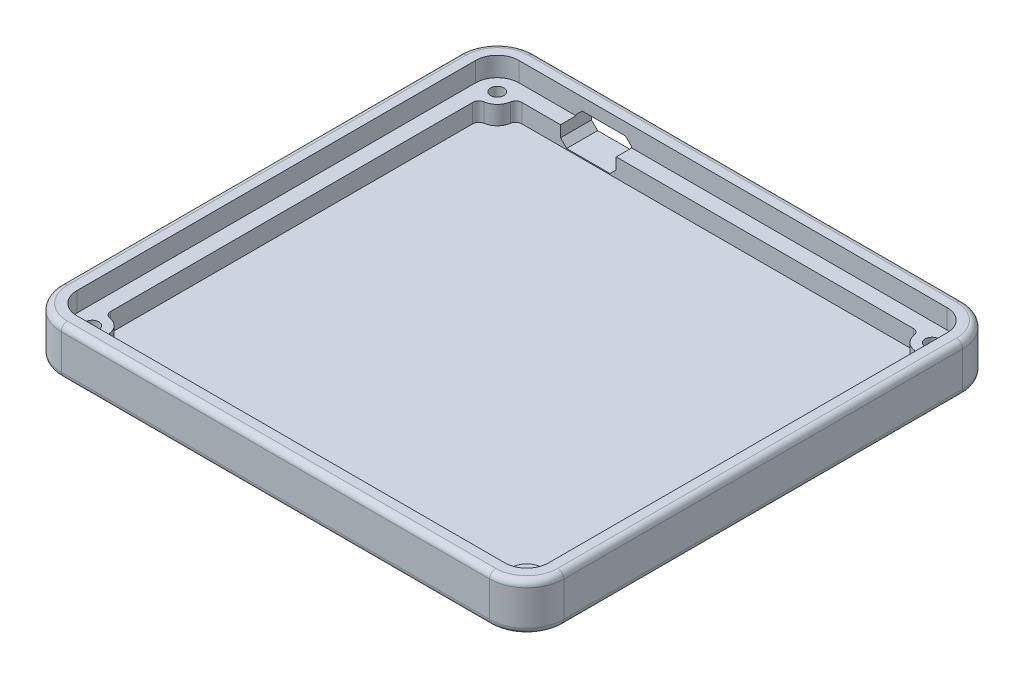
SolidWorks part; units mm, degrees
material "ABS"
ref_plane "Front Plane" through (0, 0, 0) normal (0, 0, 1) x (1, 0, 0)
ref_plane "Top Plane" through (0, 0, 0) normal (0, 1, 0) x (1, 0, 0)
ref_plane "Right Plane" through (0, 0, 0) normal (1, 0, 0) x (0, 0, -1)
sketch "Sketch2" plane through (0, 0, 0) normal (0, 1, 0) x (1, 0, 0)
  line L1 (-69.195, 71.435) -> (69.195, 71.435)
  line L2 (-76.195, 64.435) -> (-76.195, -64.435)
  line L3 (-69.195, -71.435) -> (69.195, -71.435)
  line L4 (76.195, 64.435) -> (76.195, -64.435)
  line L5 (-76.195, 71.435) -> (76.195, -71.435) construction
  line L6 (-76.195, -71.435) -> (76.195, 71.435) construction
  arc A0 (-76.195, -64.435) -> (-69.195, -71.435) centre (-69.195, -64.435) ccw
  arc A1 (-69.195, 71.435) -> (-76.195, 64.435) centre (-69.195, 64.435) ccw
  arc A2 (69.195, 71.435) -> (76.195, 64.435) centre (69.195, 64.435) cw
  arc A3 (69.195, -71.435) -> (76.195, -64.435) centre (69.195, -64.435) ccw
  point P0 (0, 0)
  dimension "D3" = 7
  dimension "D1" = 152.39
  dimension "D2" = 142.87
extrude "Boss-Extrude2" add sketch "Sketch2" along normal blind 3
sketch "Sketch3" plane through (0, 3, 0) normal (0, 1, 0) x (1, 0, 0)
  line L0 (-69.195, -71.435) -> (69.195, -71.435) construction
  line L1 (76.195, -64.435) -> (76.195, 64.435) construction
  line L2 (69.195, 71.435) -> (-69.195, 71.435) construction
  line L3 (-76.195, 64.435) -> (-76.195, -64.435) construction
  line L4 (-69.195, -71.435) -> (69.195, -71.435)
  line L5 (76.195, -64.435) -> (76.195, 64.435)
  line L6 (69.195, 71.435) -> (-69.195, 71.435)
  line L7 (-76.195, 64.435) -> (-76.195, -64.435)
  line L8 (0, -80.5945) -> (0, 82.9206) construction
  line L9 (9.041, 0) -> (-113.0904, 0) construction
  line L10 (-81.195, 64.435) -> (-81.195, -64.435)
  line L11 (-69.195, -76.435) -> (69.195, -76.435)
  line L12 (81.195, -64.435) -> (81.195, 64.435)
  line L13 (69.195, 76.435) -> (-69.195, 76.435)
  line L14 (-71.195, 60.44) -> (-71.195, -60.44)
  line L15 (-65.2, -66.435) -> (65.2, -66.435)
  line L16 (71.195, -60.44) -> (71.195, 60.44)
  line L17 (65.2, 66.435) -> (-65.2, 66.435)
  line L18 (-71.195, 60.44) -> (-70.195, 60.44)
  line L19 (-65.2, 66.435) -> (-65.2, 65.435)
  line L20 (-71.195, 64.435) -> (-71.195, -64.435) construction
  line L21 (69.195, 66.435) -> (-69.195, 66.435) construction
  line L22 (65.2, 66.435) -> (65.2, 65.435)
  line L23 (71.195, 60.44) -> (70.195, 60.44)
  line L24 (65.2, -66.435) -> (65.2, -65.435)
  line L25 (71.195, -60.44) -> (70.195, -60.44)
  line L26 (-65.2, -66.435) -> (-65.2, -65.435)
  line L27 (-71.195, -60.44) -> (-70.195, -60.44)
  line L28 (-69.195, -66.435) -> (69.195, -66.435) construction
  line L29 (71.195, -64.435) -> (71.195, 64.435) construction
  arc A0 (-76.195, -64.435) -> (-69.195, -71.435) centre (-69.195, -64.435) ccw construction
  arc A1 (69.195, -71.435) -> (76.195, -64.435) centre (69.195, -64.435) ccw construction
  arc A2 (76.195, 64.435) -> (69.195, 71.435) centre (69.195, 64.435) ccw construction
  arc A3 (-69.195, 71.435) -> (-76.195, 64.435) centre (-69.195, 64.435) ccw construction
  arc A4 (-76.195, -64.435) -> (-69.195, -71.435) centre (-69.195, -64.435) ccw
  arc A5 (69.195, -71.435) -> (76.195, -64.435) centre (69.195, -64.435) ccw
  arc A6 (76.195, 64.435) -> (69.195, 71.435) centre (69.195, 64.435) ccw
  arc A7 (-69.195, 71.435) -> (-76.195, 64.435) centre (-69.195, 64.435) ccw
  circle A9 centre (-70.2, -65.44) radius 2.15
  circle A10 centre (70.2, -65.44) radius 2.15
  circle A11 centre (70.2, 65.44) radius 2.15
  circle A12 centre (-70.2, 65.44) radius 2.15
  arc A13 (-81.195, -64.435) -> (-69.195, -76.435) centre (-69.195, -64.435) ccw
  arc A14 (69.195, -76.435) -> (81.195, -64.435) centre (69.195, -64.435) ccw
  arc A15 (81.195, 64.435) -> (69.195, 76.435) centre (69.195, 64.435) ccw
  arc A16 (-69.195, 76.435) -> (-81.195, 64.435) centre (-69.195, 64.435) ccw
  arc A21 (-70.195, 60.44) -> (-65.2, 65.435) centre (-70.195, 65.435) ccw
  arc A22 (70.195, 60.44) -> (65.2, 65.435) centre (70.195, 65.435) cw
  arc A23 (-69.195, 66.435) -> (-71.195, 64.435) centre (-69.195, 64.435) ccw construction
  arc A24 (70.195, -60.44) -> (65.2, -65.435) centre (70.195, -65.435) ccw
  arc A25 (-70.195, -60.44) -> (-65.2, -65.435) centre (-70.195, -65.435) cw
  arc A26 (-71.195, -64.435) -> (-69.195, -66.435) centre (-69.195, -64.435) ccw construction
  arc A27 (69.195, -66.435) -> (71.195, -64.435) centre (69.195, -64.435) ccw construction
  arc A28 (71.195, 64.435) -> (69.195, 66.435) centre (69.195, 64.435) ccw construction
  arc M10 (-76.195, -64.435) -> (-69.195, -71.435) centre (-69.195, -64.435) ccw
  line M11 (-69.195, -71.435) -> (69.195, -71.435)
  arc M12 (69.195, -71.435) -> (76.195, -64.435) centre (69.195, -64.435) ccw
  line M13 (76.195, -64.435) -> (76.195, 64.435)
  arc M14 (76.195, 64.435) -> (69.195, 71.435) centre (69.195, 64.435) ccw
  line M15 (69.195, 71.435) -> (-69.195, 71.435)
  arc M16 (-69.195, 71.435) -> (-76.195, 64.435) centre (-69.195, 64.435) ccw
  line M17 (-76.195, 64.435) -> (-76.195, -64.435)
  dimension "D1" = 65.44
  dimension "D2" = 4.3
  dimension "D3" = 70.2
  dimension "D4" = 5
  dimension "D6" = 1
  dimension "D7" = 5
  dimension "D8" = 1
  dimension "D9" = 5
  dimension "D5" = 5
extrude "Boss-Extrude3" add sketch "Sketch3" along normal blind 6 and the other way blind 3 contours L13 A16 L10 A13 L11 A14 L12 A15 M10 M17 M16 M15 M14 M13 M12 M11 | L17 L16 L15 L14 M17 M10 M11 M12 M13 M14 M15 M16 region at (-72.6677, 3, 67.9077) region at (-76.1033, 3, -71.3433)
sketch "Sketch8" plane through (0, 9, 0) normal (0, 1, 0) x (1, 0, 0)
  line L0 (-69.195, -76.435) -> (69.195, -76.435) construction
  line L1 (81.195, -64.435) -> (81.195, 64.435) construction
  line L2 (69.195, 76.435) -> (-69.195, 76.435) construction
  line L3 (-81.195, 64.435) -> (-81.195, -64.435) construction
  line L4 (76.195, -64.435) -> (76.195, 64.435)
  line L5 (69.195, 71.435) -> (-69.195, 71.435)
  line L6 (-76.195, 64.435) -> (-76.195, -64.435)
  line L7 (-69.195, -71.435) -> (69.195, -71.435)
  line L8 (76.195, -64.435) -> (76.195, 64.435)
  line L9 (69.195, 71.435) -> (-69.195, 71.435)
  line L10 (-76.195, 64.435) -> (-76.195, -64.435)
  line L11 (-69.195, -71.435) -> (69.195, -71.435)
  line L12 (-69.195, -76.435) -> (69.195, -76.435)
  line L13 (81.195, -64.435) -> (81.195, 64.435)
  line L14 (69.195, 76.435) -> (-69.195, 76.435)
  line L15 (-81.195, 64.435) -> (-81.195, -64.435)
  line L16 (-76.195, 64.435) -> (-76.195, -64.435)
  line L17 (-69.195, -71.435) -> (69.195, -71.435)
  line L18 (76.195, -64.435) -> (76.195, 64.435)
  line L19 (69.195, 71.435) -> (-69.195, 71.435)
  arc A0 (-81.195, -64.435) -> (-69.195, -76.435) centre (-69.195, -64.435) ccw construction
  arc A1 (69.195, -76.435) -> (81.195, -64.435) centre (69.195, -64.435) ccw construction
  arc A2 (81.195, 64.435) -> (69.195, 76.435) centre (69.195, 64.435) ccw construction
  arc A3 (-69.195, 76.435) -> (-81.195, 64.435) centre (-69.195, 64.435) ccw construction
  arc A4 (76.195, 64.435) -> (69.195, 71.435) centre (69.195, 64.435) ccw
  arc A5 (-69.195, 71.435) -> (-76.195, 64.435) centre (-69.195, 64.435) ccw
  arc A6 (-76.195, -64.435) -> (-69.195, -71.435) centre (-69.195, -64.435) ccw
  arc A7 (69.195, -71.435) -> (76.195, -64.435) centre (69.195, -64.435) ccw
  arc A8 (76.195, 64.435) -> (69.195, 71.435) centre (69.195, 64.435) ccw
  arc A9 (-69.195, 71.435) -> (-76.195, 64.435) centre (-69.195, 64.435) ccw
  arc A10 (-76.195, -64.435) -> (-69.195, -71.435) centre (-69.195, -64.435) ccw
  arc A11 (69.195, -71.435) -> (76.195, -64.435) centre (69.195, -64.435) ccw
  arc A12 (-81.195, -64.435) -> (-69.195, -76.435) centre (-69.195, -64.435) ccw
  arc A13 (69.195, -76.435) -> (81.195, -64.435) centre (69.195, -64.435) ccw
  arc A14 (81.195, 64.435) -> (69.195, 76.435) centre (69.195, 64.435) ccw
  arc A15 (-69.195, 76.435) -> (-81.195, 64.435) centre (-69.195, 64.435) ccw
  arc A16 (-76.195, -64.435) -> (-69.195, -71.435) centre (-69.195, -64.435) ccw
  arc A17 (69.195, -71.435) -> (76.195, -64.435) centre (69.195, -64.435) ccw
  arc A18 (76.195, 64.435) -> (69.195, 71.435) centre (69.195, 64.435) ccw
  arc A19 (-69.195, 71.435) -> (-76.195, 64.435) centre (-69.195, 64.435) ccw
  line M17 (69.195, 76.435) -> (-69.195, 76.435)
  arc M18 (-69.195, 76.435) -> (-81.195, 64.435) centre (-69.195, 64.435) ccw
  line M19 (-81.195, 64.435) -> (-81.195, -64.435)
  arc M20 (-81.195, -64.435) -> (-69.195, -76.435) centre (-69.195, -64.435) ccw
  line M21 (-69.195, -76.435) -> (69.195, -76.435)
  arc M22 (69.195, -76.435) -> (81.195, -64.435) centre (69.195, -64.435) ccw
  line M23 (81.195, -64.435) -> (81.195, 64.435)
  arc M24 (81.195, 64.435) -> (69.195, 76.435) centre (69.195, 64.435) ccw
  dimension "D1" = 0
  dimension "D2" = 5
extrude "Boss-Extrude4" add sketch "Sketch8" along normal blind 6.28 contours A11 L11 A10 L10 A9 L9 A8 L8 M24 M17 M18 M19 M20 M21 M22 M23 region at (-76.1033, 9, 71.3433)
sketch "Sketch9" plane through (0, 0, -76.435) normal (0, 0, -1) x (-1, 0, 0)
  line L0 (81.195, 0) -> (81.195, 15.28) construction
  line L7 (48.765, 11.345) -> (34.765, 11.345)
  line L8 (34.765, 11.345) -> (32.765, 9.345)
  line L14 (50.765, 9.345) -> (48.765, 11.345)
  line L15 (54.9775, 7.345) -> (29.0731, 7.345) construction
  line L16 (32.765, 9.345) -> (32.765, 5.345)
  line L17 (50.765, 9.345) -> (50.765, 5.345)
  line L18 (41.765, 11.345) -> (41.765, 5.8424) construction
  line L19 (-69.195, 0) -> (69.195, 0) construction
  line L20 (50.765, 5.345) -> (48.765, 3.345)
  line L21 (48.765, 3.345) -> (34.765, 3.345)
  line L22 (34.765, 3.345) -> (32.765, 5.345)
  point P7 (50.765, 7.345)
  point P20 (32.765, 7.345)
  dimension "D2" = 7.345
  dimension "D1" = 39.43
  dimension "D5" = 4
  dimension "D6" = 2
  dimension "D7" = 18
  dimension "D8" = 14
extrude "Cut-Extrude1" cut sketch "Sketch9" against normal blind 10
fillet "Fillet1" radius 2 8 edges at (-65.2, 6, -66.435) (-71.195, 6, -60.44) (-71.195, 6, 60.44) (-65.2, 6, 66.435) (71.195, 6, 60.44) (65.2, 6, 66.435) (65.2, 6, -66.435) (71.195, 6, -60.44)
sketch "Sketch11" plane through (0, 3, 0) normal (0, 1, 0) x (1, 0, 0)
  circle A0 centre (-70.2, 65.44) radius 2.15
  circle A1 centre (70.2, 65.44) radius 2.15
  circle A2 centre (70.2, -65.4964) radius 2.15
  circle A3 centre (-70.2, -65.44) radius 2.15
  dimension "D1" = 4.3
  dimension "D2" = 4.3
  dimension "D3" = 4.3
  dimension "D4" = 4.3
extrude "Cut-Extrude3" cut sketch "Sketch11" against normal through all both and the other way through all contours A3 | A2 | A1 | A0 region at (-70.2, 3, -65.44) region at (70.2, 3, -65.44) region at (70.2, 3, 65.4964) region at (-70.2, 3, 65.44)
sketch "Sketch10" plane through (0, 0, 0) normal (0, -1, 0) x (1, 0, 0)
  line L0 (0, -76.435) -> (0, 105.632) construction
  line L1 (69.195, -76.435) -> (-69.195, -76.435) construction
  line L2 (-81.195, 0) -> (91.4068, 0) construction
  line L3 (-81.195, -64.435) -> (-81.195, 64.435) construction
  line L4 (68.1793, 61.94) -> (66.1585, 65.44)
  line L5 (-66.1585, 65.44) -> (-68.1793, 68.94)
  line L6 (-68.1793, 68.94) -> (-72.2207, 68.94)
  line L7 (-72.2207, 68.94) -> (-74.2415, 65.44)
  line L8 (-74.2415, 65.44) -> (-72.2207, 61.94)
  line L9 (-72.2207, 61.94) -> (-68.1793, 61.94)
  line L10 (-68.1793, 61.94) -> (-66.1585, 65.44)
  line L11 (72.2207, 61.94) -> (68.1793, 61.94)
  line L12 (74.2415, 65.44) -> (72.2207, 61.94)
  line L13 (72.2207, 68.94) -> (74.2415, 65.44)
  line L14 (68.1793, 68.94) -> (72.2207, 68.94)
  line L15 (66.1585, 65.44) -> (68.1793, 68.94)
  line L16 (72.2207, -61.94) -> (68.1793, -61.94)
  line L17 (74.2415, -65.44) -> (72.2207, -61.94)
  line L18 (72.2207, -68.94) -> (74.2415, -65.44)
  line L19 (68.1793, -68.94) -> (72.2207, -68.94)
  line L20 (66.1585, -65.44) -> (68.1793, -68.94)
  line L21 (68.1793, -61.94) -> (66.1585, -65.44)
  line L22 (-68.1793, -61.94) -> (-66.1585, -65.44)
  line L23 (-72.2207, -61.94) -> (-68.1793, -61.94)
  line L24 (-74.2415, -65.44) -> (-72.2207, -61.94)
  line L25 (-72.2207, -68.94) -> (-74.2415, -65.44)
  line L26 (-68.1793, -68.94) -> (-72.2207, -68.94)
  line L27 (-66.1585, -65.44) -> (-68.1793, -68.94)
  line L28 (-70.2, 65.44) -> (-62.8389, 65.44)
  circle A0 centre (-70.2, 65.44) radius 3.5 construction
  circle A1 centre (-70.2, 65.44) radius 2.15 construction
  dimension "D3" = 7
extrude "Cut-Extrude2" cut sketch "Sketch10" against normal blind 4 contours L9 L10 L5 L6 L7 L8 | L12 L11 L4 L15 L14 L13 | L22 L27 L26 L25 L24 L23 | L17 L16 L21 L20 L19 L18 region at (-67.2615, 0, 63.7435)
sketch "Sketch12" plane through (0, 0, 0) normal (0, -1, 0) x (1, 0, 0)
  line L0 (-55, -65) -> (55, -65) construction
  line L1 (-55, -60) -> (55, -60)
  line L2 (-55, -70) -> (55, -70)
  line L3 (0, -65) -> (0, 6.3841) construction
  arc A0 (-55, -60) -> (-55, -70) centre (-55, -65) ccw
  arc A1 (55, -70) -> (55, -60) centre (55, -65) ccw
  point P2 (0, -65)
  dimension "D1" = 65
  dimension "D2" = 110
  dimension "D3" = 10
extrude "Cut-Extrude4" cut sketch "Sketch12" against normal blind 2
fillet "Fillet4" radius 2 16 edges at (-77.6803, 0, -72.9203) (0, 0, -76.435) (77.6803, 0, -72.9203) (81.195, 0, 0) (77.6803, 0, 72.9203) (0, 0, 76.435) (-77.6803, 0, 72.9203) (-77.6803, 15.28, -72.9203) (0, 15.28, -76.435) (77.6803, 15.28, -72.9203) (81.195, 15.28, 0) (77.6803, 15.28, 72.9203) (0, 15.28, 76.435) (-77.6803, 15.28, 72.9203) (-81.195, 0, 0) (-81.195, 15.28, 0)
